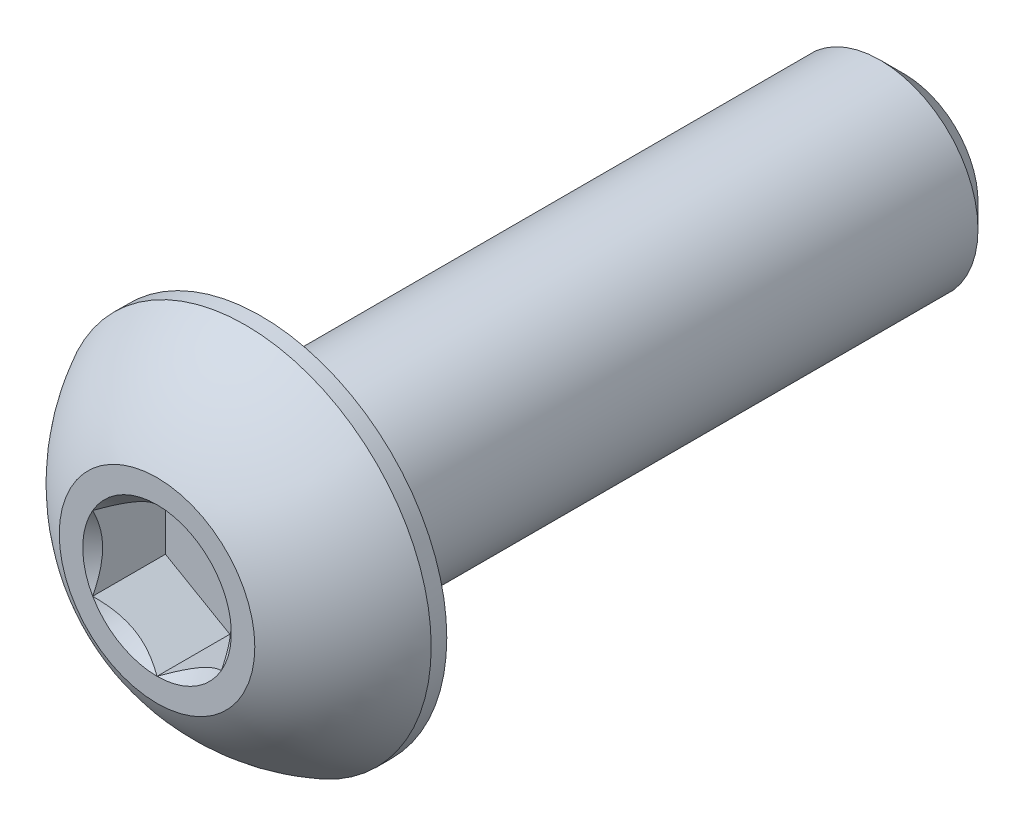
SolidWorks part; units mm, degrees
ref_plane "Front" through (0, 0, 0) normal (0, 0, 1) x (1, 0, 0)
ref_plane "Top" through (0, 0, 0) normal (0, 1, 0) x (1, 0, 0)
ref_plane "Right" through (0, 0, 0) normal (1, 0, 0) x (0, 0, -1)
sketch "Sketch1" plane through (0, 0, 0) normal (1, 0, 0) x (0, 0, -1)
  line L2 (2.5654, 2.413) -> (18.4404, 2.413)
  line L3 (18.4404, 2.413) -> (18.4404, 0)
  line L4 (18.4404, 0) -> (2.5654, 0)
  line L6 (2.1806, 4.5847) -> (2.5654, 4.5847) construction
  line L7 (18.4404, 2.413) -> (18.4404, -2.413) construction
  line L8 (0, 0) -> (2.5654, 0) construction
  line L9 (2.5654, 4.5847) -> (2.5654, -4.5847) construction
  line L11 (2.5654, 2.413) -> (2.5654, 0)
  line L13 (0, 1.5875) -> (0, -1.5875) construction
  line L14 (0, 1.5875) -> (0, 2.413) construction
  arc A3 (0, 2.413) -> (2.1806, 4.5847) centre (4.5749, 0) cw construction
  dimension "D1" = 0.3848
revolve "Revolve1" add sketch "Sketch1" angle 360 mid plane about L4
sketch "Sketch3" plane through (0, 0, -18.4404) normal (0, 0, -1) x (-1, 0, 0)
  circle A0 centre (0, 0) radius 2.413
curve "Helix/Spiral1" pitch 0.7937 height 16.6687 turns 21
sketch "Sketch2" plane through (0, 0, 0) normal (1, 0, 0) x (0, 0, -1)
  line L0 (18.4404, 2.413) -> (19.1349, 2.413)
  line L1 (19.1349, 2.413) -> (18.8373, 1.8974)
  line L2 (18.8373, 1.8974) -> (18.7381, 1.8974)
  line L3 (18.7381, 1.8974) -> (18.4404, 2.413)
  line L4 (18.5892, 2.1552) -> (18.9861, 2.1552) construction
  dimension "D1" = 60
  dimension "D2" = 0.0992
  dimension "D3" = 0.3969
chamfer "Chamfer1" distance 0.5953 angle 45 1 edges at (0, 2.413, -18.4404)
sweep "Cut-Sweep1" [suppressed] cut profiles "Sketch2" path "Helix/Spiral1"
sketch "Sketch7" plane through (0, 0, 0) normal (1, 0, 0) x (0, 0, -1)
  line L6 (2.1806, 4.5847) -> (2.5654, 4.5847) construction
  line L8 (0, 0) -> (2.5654, 0) construction
  line L11 (2.5654, 4.5847) -> (2.5654, -4.5847) construction
  line L12 (2.1806, 4.5847) -> (2.5654, 4.5847)
  line L13 (0, 0) -> (2.5654, 0)
  line L14 (0, 1.5875) -> (0, -1.5875) construction
  line L15 (2.5654, 4.5847) -> (2.5654, 0)
  line L16 (0, 2.413) -> (0, 0)
  arc A2 (2.1806, 4.5847) -> (0, 2.413) centre (4.5749, 0) ccw construction
  arc A3 (2.1806, 4.5847) -> (0, 2.413) centre (4.5749, 0) ccw
revolve "Revolve2" add sketch "Sketch7" angle 360 mid plane about L13
sketch "Sketch5" plane through (0, 0, 0) normal (0, 0, 1) x (1, 0, 0)
  line L1 (1.5875, -0.9165) -> (1.5875, 0.9165)
  line L2 (1.5875, 0.9165) -> (0, 1.8331)
  line L3 (0, 1.8331) -> (-1.5875, 0.9165)
  line L4 (-1.5875, 0.9165) -> (-1.5875, -0.9165)
  line L5 (-1.5875, -0.9165) -> (0, -1.8331)
  line L6 (0, -1.8331) -> (1.5875, -0.9165)
  circle A0 centre (0, 0) radius 1.5875 construction
extrude "Cut-Extrude2" cut sketch "Sketch5" against normal blind 1.7958
sketch "Sketch6" plane through (0, 0, 0) normal (0, 0, 1) x (1, 0, 0)
  circle A0 centre (0, 0) radius 1.8331
extrude "Cut-Extrude3" cut sketch "Sketch6" against normal blind 1.7958 draft 45
sketch "Sketch9" [suppressed] plane through (0, 0, -5.0546) normal (0, 0, 1) x (1, 0, 0)
  circle A2 centre (0, 0) radius 4.7625
extrude "Boss-Extrude2" [suppressed] add sketch "Sketch9" against normal offset from surface (12.7 mm away) 31.75
sketch "Sketch10" plane through (0, 0, 0) normal (1, 0, 0) x (0, 0, -1)
  line L0 (18.4404, 2.413) -> (18.4404, -2.413) construction
  point P0 (17.2498, -2.413)
  dimension "D1" = 1.1906
equation "\"D3@Helix/Spiral1\" = \"Lg@Sketch1\" + \"D4@Helix/Spiral1\""
equation "\"D2@Sketch2\" = \"D4@Helix/Spiral1\" * .125"
equation "\"D3@Sketch2\" = \"D4@Helix/Spiral1\" * .5"
equation "\"D1@Chamfer1\" = \"D4@Helix/Spiral1\" * .75"
equation "\"D1@Cut-Extrude2\" = \"Head Ht@Sketch1\" * .7"
equation "\"D1@Sketch1\" = \"Head Ht@Sketch1\" * .15"
equation "\"D1@Sketch10\" = \"D4@Helix/Spiral1\" * 1.5"
equation "\"D1@Cut-Extrude3\" = \"D1@Cut-Extrude2\""
